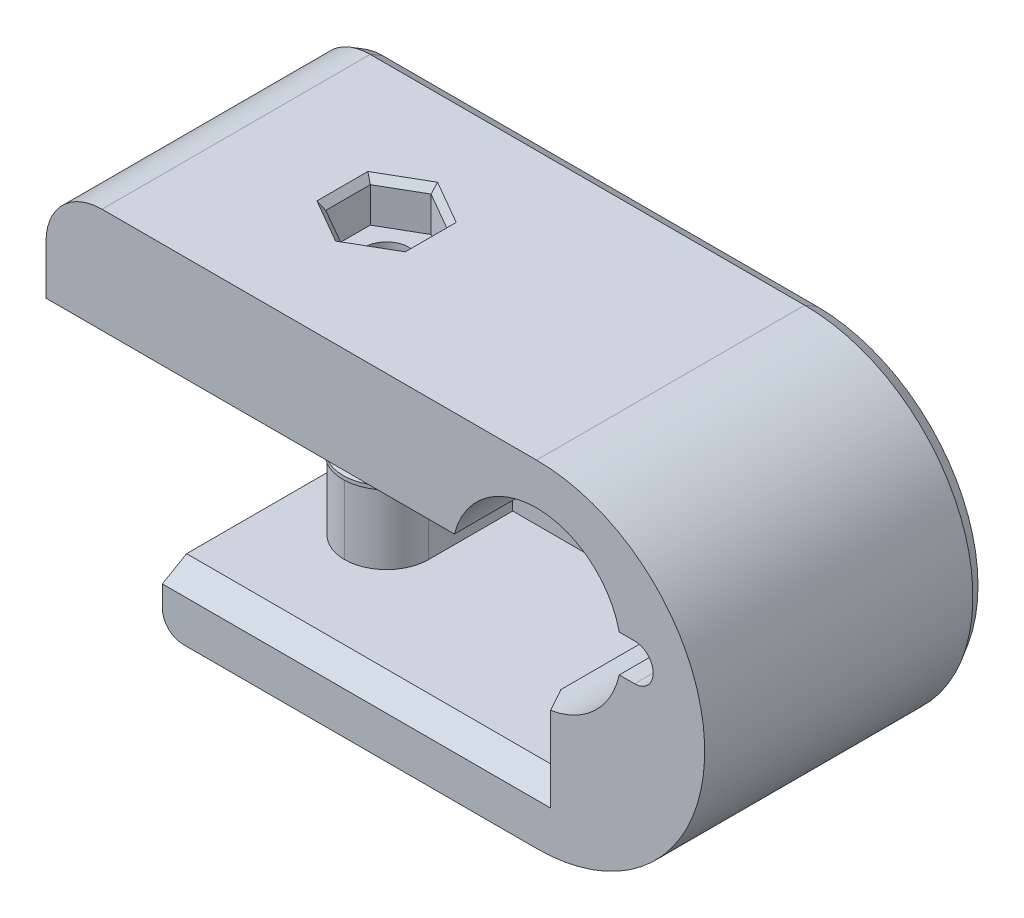
SolidWorks part; units mm, degrees
material "Custom Plastic"
ref_plane "Front Plane" through (0, 0, 0) normal (0, 0, 1) x (1, 0, 0)
ref_plane "Top Plane" through (0, 0, 0) normal (0, 1, 0) x (1, 0, 0)
ref_plane "Right Plane" through (0, 0, 0) normal (1, 0, 0) x (0, 0, -1)
sketch "Sketch1" plane through (0, 0, 0) normal (0, 0, 1) x (1, 0, 0)
  line L0 (5.9035, -1.3233) -> (7, -1.3233)
  line L1 (0, 9) -> (-31, 9)
  line L3 (0, -15) -> (-26.7, -15)
  line L4 (-26.7, -6) -> (-26.7, -15)
  line L5 (-41.6611, -6) -> (7.1, -6) construction
  line L6 (-41.6611, -6) -> (-41.6611, -11) construction
  line L7 (-41.6611, -11) -> (7.1, -11) construction
  line L8 (7.1, -6) -> (7.1, -11) construction
  line L9 (-20, 15.6207) -> (-20, -19.311) construction
  line L10 (7, 1.3233) -> (5.9035, 1.3233)
  line L11 (-25, -4.25) -> (-15, -4.25) construction
  line L12 (-25, -4.25) -> (-25, -0.25) construction
  line L13 (-15, -4.25) -> (-15, -0.25) construction
  line L14 (-25, -0.25) -> (-15, -0.25) construction
  line L15 (-25, -4.25) -> (-15, -0.25) construction
  line L16 (-15, -4.25) -> (-25, -0.25) construction
  line L17 (-5.8611, -1.5) -> (-10.9, -6)
  line L18 (-10.9, -6) -> (-26.7, -6)
  line L20 (-5.8611, 1.5) -> (-35, 1.5)
  line L21 (-35, 1.5) -> (-35, 5)
  arc A0 (5.9035, 1.3233) -> (-5.8611, 1.5) centre (0, 0) ccw
  arc A1 (7, -1.3233) -> (7, 1.3233) centre (7, 0) ccw
  arc A2 (-5.8611, -1.5) -> (5.9035, -1.3233) centre (0, 0) ccw
  arc A3 (0, -15) -> (0, 9) centre (0, -3) ccw
  arc A4 (-31, 9) -> (-35, 5) centre (-31, 5) ccw
  point P18 (-20, -2.25)
  dimension "D1" = 12.1
  dimension "D16" = 4
  dimension "D12" = 12
  dimension "D2" = 6
  dimension "D3" = 5
  dimension "D4" = 7.1
  dimension "D5" = 20
  dimension "D6" = 4
  dimension "D7" = 10
  dimension "D8" = 1.75
  dimension "D9" = 4
  dimension "D10" = 10.9
  dimension "D11" = 1.75
  dimension "D13" = 7
  dimension "D14" = 35
  dimension "D15" = 1.7
extrude "Boss-Extrude1" add sketch "Sketch1" along normal blind 20
sketch "Sketch2" plane through (0, 0, 20) normal (0, 0, 1) x (1, 0, 0)
  line L0 (-26.7, -6) -> (-26.7, -15) construction
  line L1 (-26.7, -6) -> (-23.7, -6)
  line L2 (-26.7, -6) -> (-26.7, -11)
  line L3 (-26.7, -11) -> (-23.7, -11)
  line L6 (-20.7, -18.4336) -> (-20.7, 0) construction
  line L7 (-17.7, -11) -> (-17.7, -6)
  line L8 (-23.7, -11) -> (-23.7, -6)
  line L9 (-17.7, -11) -> (0, -11)
  line L10 (-17.7, -18.4336) -> (-17.7, 0) construction
  line L11 (-23.7, -18.4336) -> (-23.7, 0) construction
  line L12 (-17.7, -6) -> (-10.9, -6)
  line L14 (0, 0) -> (-5.8611, -1.5)
  line L15 (-5.8611, -1.5) -> (-10.9, -6)
  line L16 (0, 0) -> (0, -11)
  dimension "D1" = 5
  dimension "D4" = 20.7
  dimension "D5" = 3
  dimension "D6" = 3
extrude "Cut-Extrude1" cut sketch "Sketch2" against normal offset from surface (16 mm away) 4 up to face at (-9.8986, -1.1908, 0)
sketch "Sketch3" plane through (0, 0, 20) normal (0, 0, 1) x (1, 0, 0)
  line L1 (-23.7, -11) -> (-17.7, -11)
  line L2 (-23.7, -11) -> (-23.7, -6)
  line L3 (-23.7, -6) -> (-17.7, -6)
  line L4 (-17.7, -11) -> (-17.7, -6)
extrude "Cut-Extrude2" cut sketch "Sketch3" against normal blind 7
fillet "Fillet1" radius 3 2 edges at (-17.7, -8.5, 13) (-23.7, -8.5, 13)
sketch "Sketch4" plane through (-1.2719, 0, 0) normal (0, 1, 0) x (1, 0, 0)
  circle A0 centre (-19.4281, -10) radius 1.6
  circle A1 centre (-19.4281, -10) radius 3 construction
  dimension "D1" = 3.2
extrude "Cut-Extrude3" cut sketch "Sketch4" against normal through all and the other way through all
sketch "Sketch5" plane through (-1.2719, 0, 0) normal (0, 1, 0) x (1, 0, 0)
  line L1 (-19.4281, -13.1754) -> (-16.6781, -11.5877)
  line L2 (-16.6781, -11.5877) -> (-16.6781, -8.4123)
  line L3 (-16.6781, -8.4123) -> (-19.4281, -6.8246)
  line L4 (-19.4281, -6.8246) -> (-22.1781, -8.4123)
  line L5 (-22.1781, -8.4123) -> (-22.1781, -11.5877)
  line L6 (-22.1781, -11.5877) -> (-19.4281, -13.1754)
  circle A0 centre (-19.4281, -10) radius 2.75 construction
  circle A1 centre (-19.4281, -10) radius 1.6 construction
  dimension "D1" = 5.5
extrude "Cut-Extrude4" cut sketch "Sketch5" against normal offset from surface (10 mm away) 21 from offset 16 up to face at (-20.7, -15, 11.6)
fillet "Fillet2" [suppressed] radius 12
fillet "Fillet3" radius 1.5 1 edges at (-26.7, -15, 10)
sketch "Sketch6" plane through (0, 1.5, 0) normal (0, -1, 0) x (1, 0, 0)
  line L0 (-17.7, 2.476) -> (-17.7, 5.8757) construction
  line L1 (-17.7, 4) -> (-17.7, 10) construction
  line L2 (-23.7, 2.476) -> (-23.7, 5.8757) construction
  line L3 (-23.7, 4) -> (-23.7, 10) construction
  circle A0 centre (-20.7, 10) radius 3.1
  circle A1 centre (-20.7, 10) radius 1.6
  circle A2 centre (-20.7, 10) radius 1.6 construction
  arc A3 (-23.7, 5.8757) -> (-17.7, 5.8757) centre (-20.7, 10) ccw construction
  arc A4 (-23.7, 2.476) -> (-17.7, 2.476) centre (-20.7, 10) ccw construction
  dimension "D1" = 1.5
  dimension "D2" = 5.1
  dimension "D3" = 3
extrude "Boss-Extrude2" add sketch "Sketch6" along normal blind 1.75
sketch "Sketch7" plane through (0, -6, 0) normal (0, 1, 0) x (1, 0, 0)
  line L0 (-23.7, -5.8757) -> (-23.7, -2.476) construction
  line L1 (-23.7, -4) -> (-23.7, -10) construction
  line L2 (-17.7, -2.476) -> (-17.7, -5.8757) construction
  line L3 (-17.7, -4) -> (-17.7, -10) construction
  circle A0 centre (-20.7, -10) radius 1.6
  circle A1 centre (-20.7, -10) radius 3.1
  circle A2 centre (-20.7, -10) radius 1.6 construction
  arc A3 (-17.7, -5.8757) -> (-23.7, -5.8757) centre (-20.7, -10) ccw construction
  arc A4 (-17.7, -2.476) -> (-23.7, -2.476) centre (-20.7, -10) ccw construction
  dimension "D1" = 1.5
  dimension "D2" = 5.1
  dimension "D3" = 3
extrude "Boss-Extrude3" add sketch "Sketch7" along normal blind 1.75
chamfer "Chamfer1" distance 1.5 angle 40 2 edges at (-23.8, -4.25, 10) (-17.6, -0.25, 10) first distance on face at (-23.8, -4.25, 10) first distance on face at (-17.6, -0.25, 10)
chamfer "Chamfer2" distance 1.875 angle 45 1 edges at (-20.7, -15, 11.6)
chamfer "Chamfer3" distance 1 angle 60 2 edges at (-13.35, -11, 20) (0, -8.525, 20) first distance on face at (-9.7714, -2.762, 20)
chamfer "Chamfer4" distance 0.5 angle 60 15 edges at (12, -3, 0) (-15.5, 9, 0) (-33.8284, 7.8284, 0) (-35, 3.25, 0) (-20.4306, 1.5, 0) (0.0908, 6.0493, 0) (6.4517, 1.3233, 0) (8.3233, 0, 0) (6.4517, -1.3233, 0) (0.0908, -6.0493, 0) (-8.3806, -3.75, 0) (-18.8, -6, 0) (-26.7, -9.75, 0) (-26.2607, -14.5607, 0) (-12.6, -15, 0) first distance on face at (-10.9394, -2.0321, 0)
chamfer "Chamfer6" distance 0.3 distance2 1 1 edges at (-26.7, -8.5, 4) first distance on face at (-25.2, -8.5, 4)
sketch "Sketch8" plane through (0, -6, 0) normal (0, 1, 0) x (1, 0, 0)
  line L0 (-23.7, -5.8757) -> (-23.7, -3.5649)
  line L1 (-17.7, -5.8757) -> (-17.7, -3.5649)
  line L2 (-17.7, -4) -> (-17.7, -9.219) construction
  line L5 (-23.7, -4) -> (-23.7, -9.219) construction
  arc A0 (-17.7, -5.8757) -> (-23.7, -5.8757) centre (-20.7, -10) ccw
  arc A1 (-17.7, -3.5649) -> (-23.7, -3.5649) centre (-20.7, -10) ccw
  dimension "D1" = 10.2
  dimension "D2" = 2
extrude "Boss-Extrude4" add sketch "Sketch8" along normal blind 0.5
sketch "Sketch9" plane through (0, 1.5, 0) normal (0, -1, 0) x (1, 0, 0)
  line L0 (-23.7, 3.5649) -> (-23.7, 5.8757)
  line L1 (-17.7, 3.5649) -> (-17.7, 5.8757)
  arc A0 (-23.7, 5.8757) -> (-17.7, 5.8757) centre (-20.7, 10) ccw
  arc A1 (-23.7, 3.5649) -> (-17.7, 3.5649) centre (-20.7, 10) ccw
  arc A2 (-23.7, 5.8757) -> (-17.7, 5.8757) centre (-20.7, 10) ccw construction
  arc A3 (-23.7, 3.5649) -> (-17.7, 3.5649) centre (-20.7, 10) ccw construction
extrude "Boss-Extrude5" add sketch "Sketch9" along normal blind 0.5
chamfer "Chamfer7" distance 0.5 angle 70 6 edges at (-17.7, -5.5, 4.7203) (-23.7, -5.5, 4.7203) (-20.7, -5.5, 2.9) (-17.7, 1, 4.7203) (-23.7, 1, 4.7203) (-20.7, 1, 2.9) first distance on face at (-17.7, -7, 6.2334) first distance on face at (-23.7, -7, 6.2334) first distance on face at (-20.7, -5.75, 3.2325) first distance on face at (-17.7, 1.25, 4.7203) first distance on face at (-23.7, 1.25, 4.7203) first distance on face at (-20.7, 1.25, 3.2325)
chamfer "Chamfer8" distance 0.5 distance2 0.4 6 edges at (-22.075, 9, 12.3816) (-19.325, 9, 12.3816) (-17.95, 9, 10) (-19.325, 9, 7.6184) (-22.075, 9, 7.6184) (-23.45, 9, 10) first distance on face at (-22.075, 7.5, 12.3816) first distance on face at (-19.325, 7.5, 12.3816) first distance on face at (-17.95, 7.5, 10) first distance on face at (-19.325, 7.5, 7.6184) first distance on face at (-22.075, 7.5, 7.6184) first distance on face at (-23.45, 7.5, 10)
sketch "Sketch10" plane through (0, 6, 0) normal (0, 1, 0) x (1, 0, 0)
  line L0 (-20.7, -10) -> (-19.5686, -11.1314)
  line L1 (-19.5686, -11.1314) -> (-20.3573, -11.92)
  line L2 (-20.3573, -11.92) -> (-21.0427, -11.92)
  line L3 (-21.0427, -11.92) -> (-21.8314, -11.1314)
  line L4 (-21.8314, -11.1314) -> (-20.7, -10)
  line L5 (-20.7, -10) -> (-20.7, -11.92) construction
  circle A0 centre (-20.7, -10) radius 1.6 construction
  point P8 (-20.7, -11.6)
  dimension "D1" = 0.32
extrude "Cut-Extrude5" cut sketch "Sketch10" against normal through all
equation "\"y-plate-thickness\"=5"
equation "\"bed-plate-thickness\"=3"
equation "\"x-plate-thickness\"=5"
equation "\"D3@Sketch1\"=\"x-plate-thickness\""
equation "\"rod-diameter\"=12"
equation "\"D2@Sketch1\"=\"rod-diameter\"/2"
equation "\"D1@Sketch2\"=\"x-plate-thickness\""
equation "\"D1@Sketch1\"=\"rod-diameter\"+0.1"
equation "\"D12@Sketch1\"=\"rod-diameter\""
equation "\"D14@Sketch1\"=\"x-plate-thickness\"+30"
